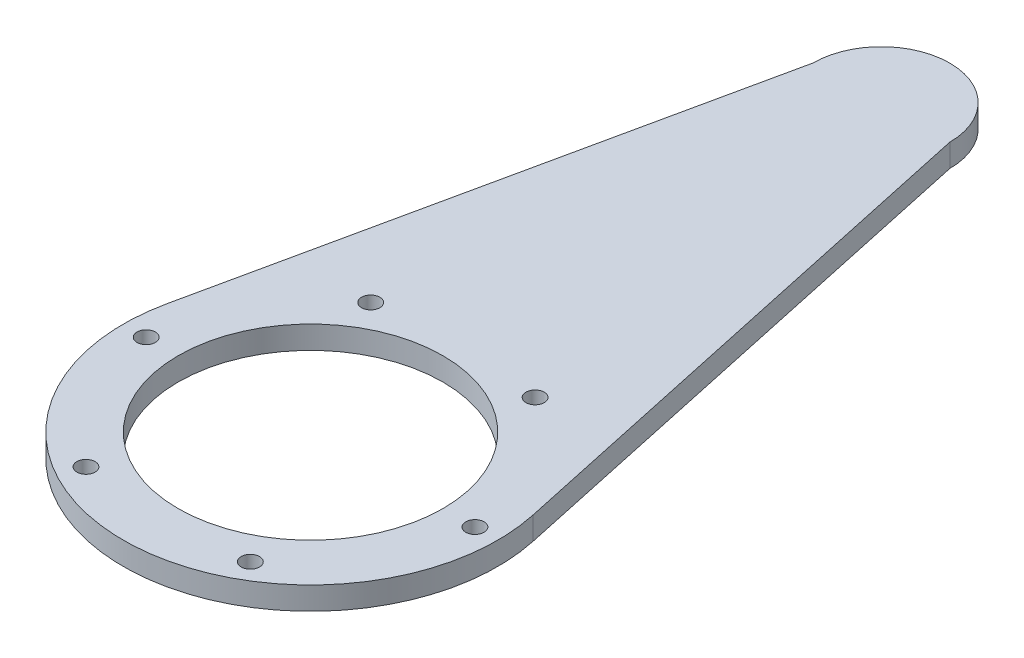
SolidWorks part; units mm, degrees
ref_plane "Front Plane" through (0, 0, 0) normal (0, 0, 1) x (1, 0, 0)
ref_plane "Top Plane" through (0, 0, 0) normal (0, 1, 0) x (1, 0, 0)
ref_plane "Right Plane" through (0, 0, 0) normal (1, 0, 0) x (0, 0, -1)
sketch "Sketch1" plane through (0, 0, 0) normal (0, 1, 0) x (1, 0, 0)
  line L0 (0, 0) -> (36, 0) construction
  line L1 (0, 0) -> (0, 125) construction
  line L2 (-15, 125) -> (-40.0796, 8.6384)
  line L3 (15, 125) -> (40.0796, 8.6384)
  arc A0 (-40.0796, 8.6384) -> (40.0796, 8.6384) centre (0, 0) ccw
  circle A1 centre (0, 0) radius 29
  circle A3 centre (36, 0) radius 2
  circle A4 centre (18, -31.1769) radius 2
  circle A5 centre (-18, -31.1769) radius 2
  circle A6 centre (-36, 0) radius 2
  circle A7 centre (-18, 31.1769) radius 2
  circle A8 centre (18, 31.1769) radius 2
  arc A9 (15, 125) -> (-15, 125) centre (0, 125) ccw
  point P19 (0, 0)
  dimension "D1" = 82
  dimension "D2" = 58
  dimension "D4" = 4
  dimension "D7" = 30
  dimension "D3" = 36
  dimension "D6" = 125
  dimension "D5" = 6
extrude "Boss-Extrude1" add sketch "Sketch1" along normal blind 5
ref_axis "Axis1" through (0, 5, 0) along (0, -1, 0)
ref_axis "Axis2" through (18, 5, -31.1769) along (0, -1, 0)
